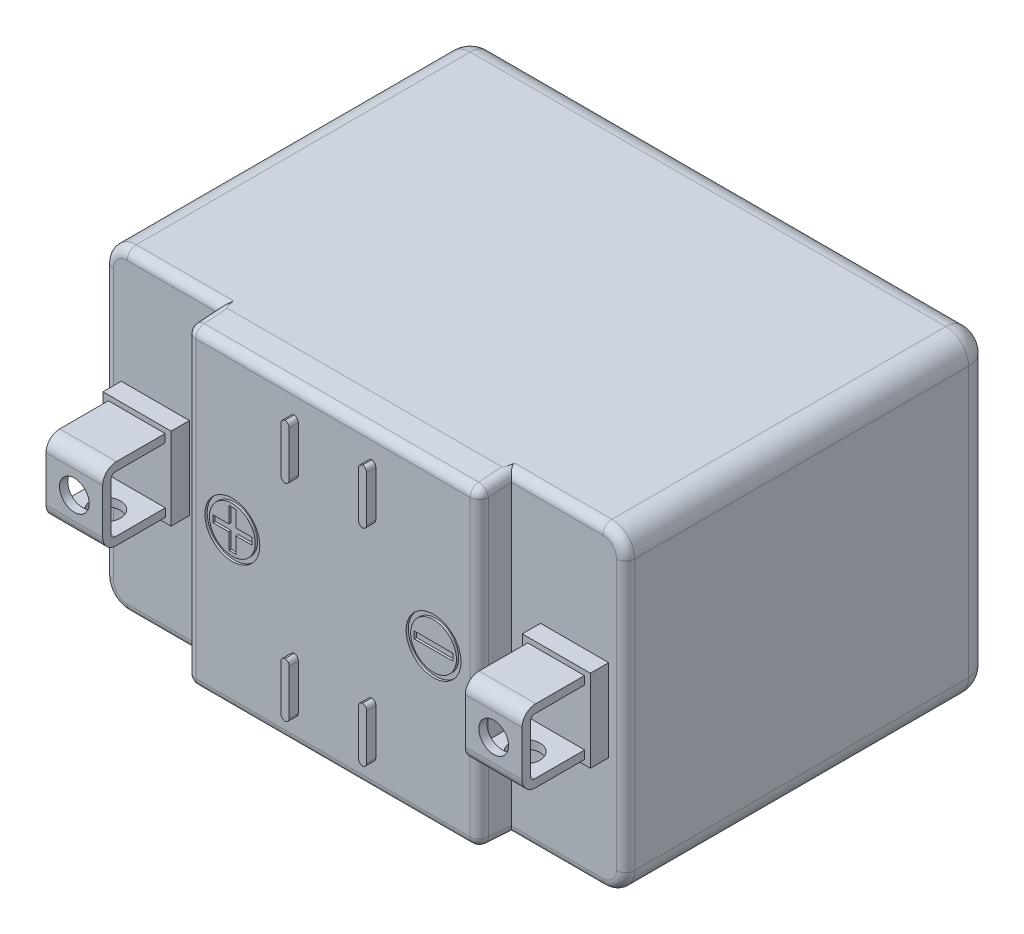
SolidWorks part; units mm, degrees
ref_plane "Спереди" through (0, 0, 0) normal (0, 0, 1) x (1, 0, 0)
ref_plane "Сверху" through (0, 0, 0) normal (0, 1, 0) x (1, 0, 0)
ref_plane "Справа" through (0, 0, 0) normal (1, 0, 0) x (0, 0, -1)
sketch "Эскиз1" plane through (0, 0, 0) normal (0, 0, 1) x (1, 0, 0)
  line L1 (-57, 34.5) -> (57, 34.5)
  line L2 (-57, 34.5) -> (-57, -34.5)
  line L3 (-57, -34.5) -> (57, -34.5)
  line L4 (57, 34.5) -> (57, -34.5)
  line L5 (0, -34.5) -> (0, 34.5) construction
  line L6 (-57, 0) -> (57, 0) construction
  point P0 (0, 0)
  dimension "D1" = 69
  dimension "D2" = 114
extrude "Бобышка-Вытянуть1" add sketch "Эскиз1" along normal blind 80
fillet "Скругление1" radius 5 8 edges at (57, 0, 0) (0, 34.5, 0) (-57, 0, 0) (0, -34.5, 0) (57, -34.5, 40) (57, 34.5, 40) (-57, 34.5, 40) (-57, -34.5, 40)
sketch "Эскиз2" plane through (0, 0, 80) normal (0, 0, 1) x (1, 0, 0)
  line L0 (-52, -34.5) -> (52, -34.5) construction
  line L1 (-32, 34.5) -> (32, 34.5)
  line L2 (-32, 34.5) -> (-32, -34.5)
  line L3 (-32, -34.5) -> (32, -34.5)
  line L4 (32, 34.5) -> (32, -34.5)
  line L5 (0, -34.5) -> (0, 34.5) construction
  line L6 (-32, 0) -> (32, 0) construction
  point P0 (0, 0)
  dimension "D1" = 64
extrude "Бобышка-Вытянуть2" add sketch "Эскиз2" along normal blind 7
sketch "Эскиз3" plane through (0, 0, 87) normal (0, 0, 1) x (1, 0, 0)
  line L0 (0, 0) -> (0, 34.5) construction
  line L1 (-9.375, 28.5) -> (-7.575, 28.5)
  line L2 (-9.375, 28.5) -> (-9.375, 16.6)
  line L3 (-9.375, 16.6) -> (-7.575, 16.6)
  line L4 (-7.575, 28.5) -> (-7.575, 16.6)
  line L6 (0, 0) -> (32, 0) construction
  line L8 (7.575, 28.5) -> (7.575, 16.6)
  line L9 (9.375, 16.6) -> (7.575, 16.6)
  line L10 (9.375, 28.5) -> (9.375, 16.6)
  line L11 (9.375, 28.5) -> (7.575, 28.5)
  line L13 (9.375, -28.5) -> (7.575, -28.5)
  line L14 (9.375, -28.5) -> (9.375, -16.6)
  line L15 (9.375, -16.6) -> (7.575, -16.6)
  line L16 (7.575, -28.5) -> (7.575, -16.6)
  line L17 (-7.575, -28.5) -> (-7.575, -16.6)
  line L18 (-9.375, -16.6) -> (-7.575, -16.6)
  line L19 (-9.375, -28.5) -> (-9.375, -16.6)
  line L20 (-9.375, -28.5) -> (-7.575, -28.5)
  line L21 (32, 34.5) -> (-32, 34.5) construction
  line L22 (32, -34.5) -> (32, 34.5) construction
  dimension "D1" = 1.8
  dimension "D2" = 11.9
  dimension "D3" = 15.15
  dimension "D4" = 6
extrude "Бобышка-Вытянуть3" add sketch "Эскиз3" along normal blind 2
fillet "Скругление3" radius 1 16 edges at (-7.575, -16.6, 88) (-9.375, -16.6, 88) (-9.375, -28.5, 88) (-7.575, -28.5, 88) (7.575, -16.6, 88) (7.575, -28.5, 88) (9.375, -28.5, 88) (9.375, -16.6, 88) (7.575, 16.6, 88) (9.375, 16.6, 88) (9.375, 28.5, 88) (7.575, 28.5, 88) (-7.575, 28.5, 88) (-9.375, 28.5, 88) (-7.575, 16.6, 88) (-9.375, 16.6, 88)
sketch "Эскиз4" plane through (57, 0, 0) normal (1, 0, 0) x (0, 0, -1)
  line L0 (-80.1, 34.5) -> (-87, 34)
  line L1 (-87, -34.5) -> (-87, 34.5) construction
  line L2 (-87, 34) -> (-87, 34.5)
  line L3 (-87, 34.5) -> (-80, 34.5) construction
  line L4 (-87, 34.5) -> (-80.1, 34.5)
  line L5 (-80.1, -34.5) -> (-87, -34.5)
  line L6 (-87, -34.5) -> (-87, -34)
  line L7 (-87, -34) -> (-80.1, -34.5)
  line L8 (-5, -34.5) -> (-80, -34.5) construction
  line L10 (-80, -29.5) -> (-80, -34.5) construction
  dimension "D1" = 0.5
  dimension "D2" = 0.1
extrude "Вырез-Вытянуть1" cut sketch "Эскиз4" against normal through all
fillet "Скругление4" radius 2 8 edges at (0, 34, 87) (32, 0, 87) (0, -34, 87) (-32, 0, 87) (-32, 34.25, 83.55) (32, 34.25, 83.55) (32, -34.25, 83.55) (-32, -34.25, 83.55)
fillet "Скругление6" radius 2 10 edges at (55.5355, 33.0355, 80) (57, 0, 80) (55.5355, -33.0355, 80) (-55.5355, 33.0355, 80) (-57, 0, 80) (-55.5355, -33.0355, 80)
sketch "Эскиз5" plane through (0, 0, 80) normal (0, 0, 1) x (1, 0, 0)
  line L0 (0, 0) -> (0, 34.5) construction
  line L1 (38.4, 9) -> (53.3, 9)
  line L2 (38.4, 9) -> (38.4, -9)
  line L3 (38.4, -9) -> (53.3, -9)
  line L4 (53.3, 9) -> (53.3, -9)
  line L5 (45.85, -9) -> (45.85, 9) construction
  line L6 (38.4, 0) -> (53.3, 0) construction
  line L7 (-30, 34.5) -> (30, 34.5) construction
  line L8 (-38.4, 0) -> (-53.3, 0) construction
  line L9 (-45.85, -9) -> (-45.85, 9) construction
  line L10 (-53.3, 9) -> (-53.3, -9)
  line L11 (-38.4, -9) -> (-53.3, -9)
  line L12 (-38.4, 9) -> (-38.4, -9)
  line L13 (-38.4, 9) -> (-53.3, 9)
  point P0 (45.85, 0)
  point P19 (-45.85, 0)
  dimension "D1" = 18
  dimension "D2" = 14.9
  dimension "D3" = 76.8
extrude "Бобышка-Вытянуть4" add sketch "Эскиз5" along normal blind 4
ref_plane "Плоскость1" through (45.85, 0, 0) normal (1, 0, 0) x (0, 0, -1)
sketch "Эскиз7" plane through (45.85, 0, 0) normal (1, 0, 0) x (0, 0, -1)
  line L0 (-84.0559, 7.95) -> (-97.7, 7.95)
  line L1 (-97.7, 7.95) -> (-97.7, -7.95)
  line L2 (-97.7, -7.95) -> (-84, -7.95)
  line L3 (-84, 0) -> (-97.7, 0) construction
  line L4 (-84, -9) -> (-84, 9) construction
  line L5 (-84.0559, 6.15) -> (-95.9, 6.15)
  line L6 (-95.9, 6.15) -> (-95.9, -6.15)
  line L7 (-95.9, -6.15) -> (-84, -6.15)
  line L8 (-84.0559, 7.95) -> (-84.0559, 6.15)
  line L9 (-84, -6.15) -> (-84, -7.95)
  dimension "D1" = 13.7
  dimension "D2" = 15.9
  dimension "D3" = 1.8
extrude "Бобышка-Вытянуть5" add sketch "Эскиз7" along normal mid plane 12.4
fillet "Скругление7" radius 3 2 edges at (45.85, 7.95, 97.7) (45.85, -7.95, 97.7)
fillet "Скругление8" radius 1 2 edges at (45.85, -6.15, 95.9) (45.85, 6.15, 95.9)
sketch "Эскиз8" plane through (0, 0, 97.7) normal (0, 0, 1) x (1, 0, 0)
  line L0 (39.65, -4.95) -> (52.05, 4.95) construction
  circle A0 centre (45.85, 0) radius 3.25
  dimension "D1" = 6.5
extrude "Вырез-Вытянуть2" cut sketch "Эскиз8" against normal up to next
sketch "Эскиз9" plane through (0, -7.95, 0) normal (0, -1, 0) x (1, 0, 0)
  line L0 (52.05, 97.7) -> (39.65, 84) construction
  circle A0 centre (45.85, 90.85) radius 3.25
  dimension "D1" = 6.5
extrude "Вырез-Вытянуть3" cut sketch "Эскиз9" against normal up to next
mirror "Зеркальное отражение1" about plane through (0, 0, 0) normal (1, 0, 0) of "Вырез-Вытянуть3", "Вырез-Вытянуть2", "Скругление8", "Скругление7", "Бобышка-Вытянуть5"
sketch "Эскиз10" plane through (0, 0, 87) normal (0, 0, 1) x (1, 0, 0)
  line L0 (0, 0) -> (0, 32.1397) construction
  line L1 (30, 32.1397) -> (-30, 32.1397) construction
  line L2 (-17.75, 0.75) -> (-17.75, -0.75)
  line L3 (17.75, 0.75) -> (26.25, 0.75)
  line L4 (17.75, 0.75) -> (17.75, -0.75)
  line L5 (17.75, -0.75) -> (26.25, -0.75)
  line L6 (26.25, 0.75) -> (26.25, -0.75)
  line L7 (22, -0.75) -> (22, 0.75) construction
  line L8 (17.75, 0) -> (26.25, 0) construction
  line L9 (-17.75, 0.75) -> (-21.25, 0.75)
  line L10 (-26.25, 0.75) -> (-26.25, -0.75)
  line L11 (-17.75, -0.75) -> (-21.25, -0.75)
  line L12 (-22.75, -0.75) -> (-26.25, -0.75)
  line L13 (-22.75, 4.25) -> (-21.25, 4.25)
  line L14 (-22.75, 4.25) -> (-22.75, 0.75)
  line L15 (-22.75, -4.25) -> (-21.25, -4.25)
  line L16 (-21.25, 4.25) -> (-21.25, 0.75)
  line L17 (-22, -4.25) -> (-22, 4.25) construction
  line L19 (-22.75, -0.75) -> (-22.75, -4.25)
  line L20 (-21.25, -0.75) -> (-21.25, -4.25)
  line L21 (-22.75, 0.75) -> (-26.25, 0.75)
  line L22 (-16, 0) -> (16, 0) construction
  circle A0 centre (-22, 0) radius 6
  circle A1 centre (22, 0) radius 6
  circle A2 centre (-22, 0) radius 5
  circle A3 centre (22, 0) radius 5
  dimension "D1" = 12
  dimension "D2" = 10
  dimension "D3" = 8.5
  dimension "D4" = 1.5
  dimension "D5" = 32
extrude "Вырез-Вытянуть4" cut sketch "Эскиз10" against normal blind 0.5 contours A0 A2 | L14 L21 L10 L12 L19 L15 L20 L11 L2 L9 L16 L13 | L6 L3 L4 L5 | A1 A3 region at (-22, 0, 87) region at (22, 0, 87) region at (-27.8303, 0, 87) region at (16.1697, 0, 87)
sketch "Эскиз13" plane through (0, -34.5, 0) normal (0, -1, 0) x (1, 0, 0)
  text T0 "Aliant ultralight battery\r\nYLP-14\r\nLiFEePO4"
extrude "Вырез-Вытянуть5" cut sketch "Эскиз13" against normal blind 0.5
